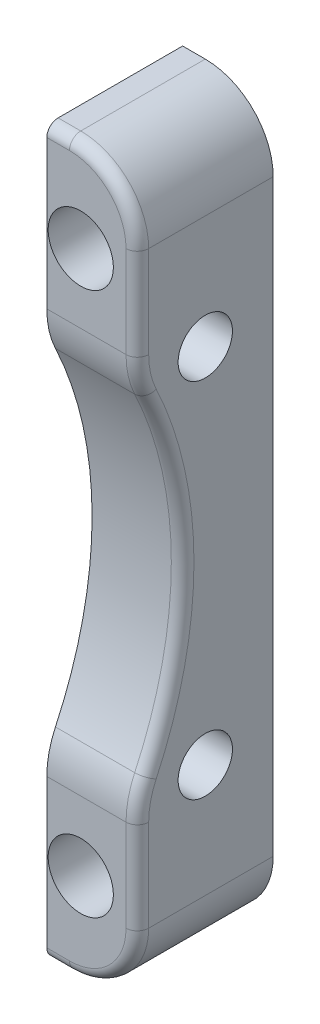
SolidWorks part; units mm, degrees
ref_plane "Front Plane" through (0, 0, 0) normal (0, 0, 1) x (1, 0, 0)
ref_plane "Top Plane" through (0, 0, 0) normal (0, 1, 0) x (1, 0, 0)
ref_plane "Right Plane" through (0, 0, 0) normal (1, 0, 0) x (0, 0, -1)
sketch "Sketch1" plane through (0, 0, 0) normal (1, 0, 0) x (0, 0, -1)
  line L0 (0, -25.4) -> (0, 25.4)
  line L1 (0, 25.4) -> (-9.525, 25.4)
  line L2 (-9.525, 25.4) -> (-9.525, 12.7)
  line L3 (0, -25.4) -> (-9.525, -25.4)
  line L4 (-9.525, -25.4) -> (-9.525, -12.7)
  arc A0 (-9.525, 12.7) -> (-9.525, -12.7) centre (-33.3375, 0) cw
  point P8 (0, 0)
  point P10 (-6.35, 0)
  dimension "D1" = 9.525
  dimension "D2" = 50.8
  dimension "D3" = 12.7
  dimension "D4" = 6.35
extrude "Boss-Extrude1" add sketch "Sketch1" along normal blind 6.35
sketch "Sketch2" plane through (0, 0, 9.525) normal (0, 0, 1) x (1, 0, 0)
  line L0 (2.3813, 19.05) -> (2.3813, -19.05) construction
  circle A0 centre (2.3813, 19.05) radius 2.286
  circle A1 centre (2.3813, -19.05) radius 2.286
  arc A2 (2.3813, 17.3228) -> (2.3813, 20.7772) centre (2.3813, 19.05) ccw construction
  point P4 (2.3813, 0)
  dimension "D1" = 4.572
extrude "Cut-Extrude1" cut sketch "Sketch2" against normal up to next
sketch "Sketch3" plane through (6.35, 0, 0) normal (1, 0, 0) x (0, 0, -1)
  circle A0 centre (-4.7625, 12.7) radius 1.905
  circle A1 centre (-4.7625, -12.7) radius 1.905
  circle A2 centre (-4.7625, 12.7) radius 2.032 construction
  circle A3 centre (-4.7625, -12.7) radius 2.032 construction
  dimension "D1" = 3.81
extrude "Cut-Extrude2" cut sketch "Sketch3" against normal up to next
fillet "Fillet1" radius 4.7625 2 edges at (6.35, -25.4, 4.7625) (6.35, 25.4, 4.7625)
fillet "Fillet2" radius 6.35 2 edges at (3.175, -12.7, 9.525) (3.175, 12.7, 9.525)
fillet "Fillet3" radius 0.7937 9 edges at (0.7937, 25.4, 9.525) (4.9551, 24.0051, 9.525) (0.7937, -25.4, 9.525) (4.9551, -24.0051, 9.525) (6.35, -17.4183, 9.525) (6.35, -12.8133, 9.372) (6.35, 0, 6.35) (6.35, 12.8133, 9.372) (6.35, 17.4183, 9.525)
